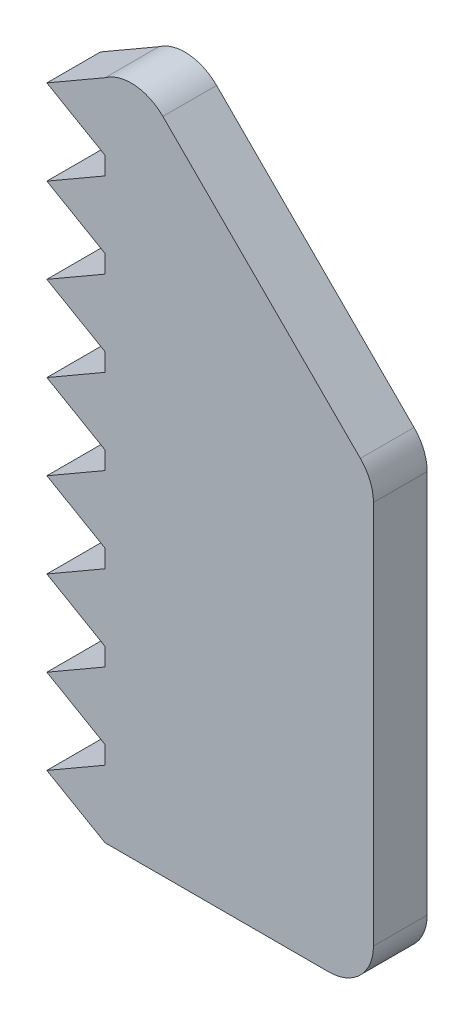
SolidWorks part; units mm, degrees
material "6061-T6 (SS)"
ref_plane "Alzado" through (0, 0, 0) normal (0, 0, 1) x (1, 0, 0)
ref_plane "Planta" through (0, 0, 0) normal (0, 1, 0) x (1, 0, 0)
ref_plane "Vista lateral" through (0, 0, 0) normal (1, 0, 0) x (0, 0, -1)
sketch "Croquis1" plane through (0, 0, 0) normal (0, 0, 1) x (1, 0, 0)
  line L0 (0, 0) -> (0, 100) construction
  line L1 (0, 100) -> (30, 70) construction
  line L2 (30, 70) -> (30, 0) construction
  line L3 (30, 0) -> (0, 0) construction
  line L4 (0, 20) -> (0, 100)
  line L5 (0, 100) -> (30, 70)
  line L6 (30, 70) -> (30, 20)
  line L7 (30, 20) -> (0, 20)
  dimension "D1" = 30
  dimension "D2" = 90
  dimension "D3" = 45
  dimension "D4" = 100
  dimension "D5" = 80
extrude "Saliente-Extruir1" add sketch "Croquis1" along normal mid plane 6
sketch "Croquis4" plane through (0, 0, 3) normal (0, 0, 1) x (1, 0, 0)
  line L0 (0, 20) -> (-6.5, 23.7528)
  line L1 (-6.5, 23.7528) -> (0, 27.5056)
  line L3 (0, 27.5056) -> (0, 20)
  line L4 (0, 37.0111) -> (0, 29.5056)
  line L5 (0, 29.5056) -> (-6.5, 33.2583)
  line L6 (-6.5, 33.2583) -> (0, 37.0111)
  line L7 (0, 46.5167) -> (0, 39.0111)
  line L8 (0, 39.0111) -> (-6.5, 42.7639)
  line L9 (-6.5, 42.7639) -> (0, 46.5167)
  line L10 (0, 56.0222) -> (0, 48.5167)
  line L11 (0, 48.5167) -> (-6.5, 52.2694)
  line L12 (-6.5, 52.2694) -> (0, 56.0222)
  line L13 (0, 65.5278) -> (0, 58.0222)
  line L14 (0, 58.0222) -> (-6.5, 61.775)
  line L15 (-6.5, 61.775) -> (0, 65.5278)
  line L16 (0, 75.0333) -> (0, 67.5278)
  line L17 (0, 67.5278) -> (-6.5, 71.2805)
  line L18 (-6.5, 71.2805) -> (0, 75.0333)
  line L19 (0, 84.5389) -> (0, 77.0333)
  line L20 (0, 77.0333) -> (-6.5, 80.7861)
  line L21 (-6.5, 80.7861) -> (0, 84.5389)
  line L22 (0, 94.0444) -> (0, 86.5389)
  line L23 (0, 86.5389) -> (-6.5, 90.2917)
  line L24 (-6.5, 90.2917) -> (0, 94.0444)
  line L34 (0, 122.5611) -> (0, 115.0555) [skipped]
  line L35 (0, 115.0555) -> (-6.5, 118.8083) [skipped]
  line L36 (-6.5, 118.8083) -> (0, 122.5611) [skipped]
  line L37 (0, 103.55) -> (0, 96.0444) [skipped]
  line L38 (0, 96.0444) -> (-6.5, 99.7972) [skipped]
  line L39 (-6.5, 99.7972) -> (0, 103.55) [skipped]
  line L40 (0, 113.0555) -> (0, 105.55) [skipped]
  line L41 (0, 105.55) -> (-6.5, 109.3028) [skipped]
  line L42 (-6.5, 109.3028) -> (0, 113.0555) [skipped]
  dimension "D1" = 6.5
  dimension "D3" = 2
  dimension "D2" = 11
extrude "Saliente-Extruir3" add sketch "Croquis4" against normal through all
fillet "Redondeo1" radius 5 3 edges at (0, 100, 0) (30, 20, 0) (30, 70, 0)
